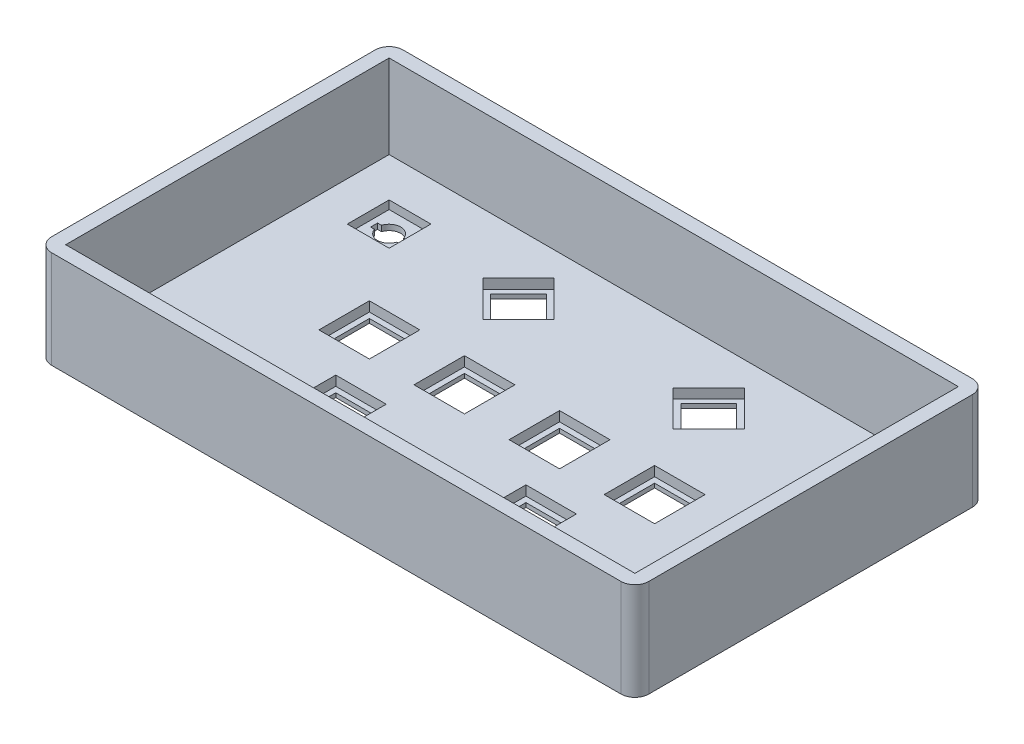
SolidWorks part; units mm, degrees
note: The reader was unsure of these and kept them because the rebuilt part matched: shared geometry of "Sketch1<3>".
ref_plane "Front Plane" through (0, 0, 0) normal (0, 0, 1) x (1, 0, 0)
ref_plane "Top Plane" through (0, 0, 0) normal (0, 1, 0) x (1, 0, 0)
ref_plane "Right Plane" through (0, 0, 0) normal (1, 0, 0) x (0, 0, -1)
sketch "Sketch1" plane through (0, 0, 0) normal (0, 1, 0) x (1, 0, 0)
  line L0 (102.0702, 127.7999) -> (102.0702, -14.5462) construction
  line L1 (0, 0) -> (204.1404, 0)
  line L2 (0, 0) -> (0, 116)
  line L3 (0, 116) -> (204.1404, 116)
  line L4 (204.1404, 0) -> (204.1404, 116)
  line L25 (67.9702, 119.0104) -> (67.9702, -4.6764) construction
  line L26 (43.8702, 65.05) -> (57.9702, 65.05)
  line L31 (43.8702, 65.05) -> (43.8702, 50.95)
  line L32 (43.8702, 50.95) -> (57.9702, 50.95)
  line L33 (25.7608, 94.4142) -> (0, 94.4142) construction
  line L34 (21.5858, 90.2392) -> (21.5858, 116) construction
  line L35 (57.9702, 65.05) -> (57.9702, 50.95)
  line L40 (41.3702, 67.55) -> (41.3702, 48.45) construction
  line L41 (41.3702, 48.45) -> (60.4702, 48.45) construction
  line L42 (60.4702, 67.55) -> (60.4702, 48.45) construction
  line L43 (41.3702, 67.55) -> (60.4702, 67.55) construction
  line L44 (94.5702, 67.55) -> (94.5702, 48.45) construction
  line L45 (94.5702, 48.45) -> (75.4702, 48.45) construction
  line L46 (75.4702, 67.55) -> (75.4702, 48.45) construction
  line L47 (94.5702, 67.55) -> (75.4702, 67.55) construction
  line L48 (92.0702, 50.95) -> (77.9702, 50.95)
  line L49 (77.9702, 65.05) -> (77.9702, 50.95)
  line L50 (92.0702, 65.05) -> (77.9702, 65.05)
  line L51 (92.0702, 65.05) -> (92.0702, 50.95)
  line L52 (13.3874, 28.9) -> (54.844, 28.9) construction
  line L53 (60.9202, 35.95) -> (75.0202, 35.95)
  line L54 (60.9202, 35.95) -> (60.9202, 21.85)
  line L63 (60.9202, 21.85) -> (75.0202, 21.85)
  line L64 (-34.0049, 58) -> (152.0549, 58) construction
  line L65 (75.0202, 35.95) -> (75.0202, 21.85)
  line L66 (48.8702, 38.45) -> (87.0702, 38.45) construction
  line L67 (48.8702, 38.45) -> (48.8702, 19.35) construction
  line L68 (48.8702, 19.35) -> (87.0702, 19.35) construction
  line L69 (87.0702, 38.45) -> (87.0702, 19.35) construction
  line L70 (155.2702, 19.35) -> (117.0702, 19.35) construction
  line L71 (117.0702, 38.45) -> (117.0702, 19.35) construction
  line L72 (155.2702, 38.45) -> (117.0702, 38.45) construction
  line L73 (155.2702, 38.45) -> (155.2702, 19.35) construction
  line L74 (143.2202, 21.85) -> (129.1202, 21.85)
  line L75 (129.1202, 35.95) -> (129.1202, 21.85)
  line L76 (143.2202, 35.95) -> (129.1202, 35.95)
  line L77 (143.2202, 35.95) -> (143.2202, 21.85)
  line L78 (112.0702, 65.05) -> (112.0702, 50.95)
  line L79 (112.0702, 65.05) -> (126.1702, 65.05)
  line L80 (126.1702, 65.05) -> (126.1702, 50.95)
  line L81 (112.0702, 50.95) -> (126.1702, 50.95)
  line L82 (109.5702, 48.45) -> (128.6702, 48.45) construction
  line L83 (109.5702, 67.55) -> (109.5702, 48.45) construction
  line L84 (109.5702, 67.55) -> (128.6702, 67.55) construction
  line L85 (128.6702, 67.55) -> (128.6702, 48.45) construction
  line L86 (162.7702, 48.45) -> (143.6702, 48.45) construction
  line L87 (162.7702, 67.55) -> (162.7702, 48.45) construction
  line L88 (162.7702, 67.55) -> (143.6702, 67.55) construction
  line L89 (143.6702, 67.55) -> (143.6702, 48.45) construction
  line L90 (160.2702, 50.95) -> (146.1702, 50.95)
  line L91 (146.1702, 65.05) -> (146.1702, 50.95)
  line L92 (160.2702, 65.05) -> (146.1702, 65.05)
  line L93 (160.2702, 65.05) -> (160.2702, 50.95)
  line L94 (60.4702, 55.2151) -> (75.4702, 55.2151) construction
  line L95 (94.5702, 55.2151) -> (109.5702, 55.2151) construction
  line L96 (36.5858, 106.0624) -> (36.5858, 87.3701) construction
  line L97 (67.9702, 104.3844) -> (58, 94.4142)
  line L102 (58, 94.4142) -> (67.9702, 84.444)
  line L103 (67.9702, 84.444) -> (77.9404, 94.4142)
  line L104 (77.9404, 94.4142) -> (67.9702, 104.3844)
  line L109 (79.3546, 94.4142) -> (67.9702, 105.7986) construction
  line L110 (67.9702, 105.7986) -> (56.5858, 94.4142) construction
  line L111 (56.5858, 94.4142) -> (67.9702, 83.0298) construction
  line L112 (67.9702, 83.0298) -> (79.3546, 94.4142) construction
  line L113 (136.1702, 83.0298) -> (124.7858, 94.4142) construction
  line L114 (147.5546, 94.4142) -> (136.1702, 83.0298) construction
  line L115 (136.1702, 105.7986) -> (147.5546, 94.4142) construction
  line L116 (124.7858, 94.4142) -> (136.1702, 105.7986) construction
  line L117 (136.1702, 84.444) -> (126.2, 94.4142)
  line L118 (146.1404, 94.4142) -> (136.1702, 84.444)
  line L119 (136.1702, 104.3844) -> (146.1404, 94.4142)
  line L120 (126.2, 94.4142) -> (136.1702, 104.3844)
  line L121 (-5, 0) -> (-5, 116)
  line L122 (0, 121) -> (204.1404, 121)
  line L123 (209.1404, 0) -> (209.1404, 116)
  line L124 (0, -5) -> (204.1404, -5)
  line L125 (209.1404, -5) -> (209.1404, 121) construction
  line L126 (-5, -5) -> (209.1404, -5) construction
  line L127 (-5, 121) -> (209.1404, 121) construction
  line L128 (-5, -5) -> (-5, 121) construction
  line L129 (21.5858, 94.4142) -> (58, 94.4142) construction
  line L131 (21.5858, 58) -> (21.5858, 94.4142) construction
  line L132 (16.1858, 93.1642) -> (26.9858, 93.1642)
  line L133 (16.1858, 93.1642) -> (16.1858, 95.6642)
  line L134 (16.1858, 95.6642) -> (26.9858, 95.6642)
  line L135 (26.9858, 93.1642) -> (26.9858, 95.6642)
  line L136 (16.1858, 93.1642) -> (26.9858, 95.6642) construction
  line L137 (16.1858, 95.6642) -> (26.9858, 93.1642) construction
  line L138 (177.1546, 93.1642) -> (187.9546, 93.1642)
  line L139 (177.1546, 93.1642) -> (177.1546, 95.6642)
  line L140 (177.1546, 95.6642) -> (187.9546, 95.6642)
  line L141 (187.9546, 93.1642) -> (187.9546, 95.6642)
  line L142 (177.1546, 93.1642) -> (187.9546, 95.6642) construction
  line L143 (177.1546, 95.6642) -> (187.9546, 93.1642) construction
  circle A0 centre (21.5858, 94.4142) radius 4.175
  circle A2 centre (21.5858, 94.4142) radius 15 construction
  circle A3 centre (182.5546, 94.4142) radius 15 construction
  circle A4 centre (182.5546, 94.4142) radius 4.175
  arc A6 (0, 121) -> (-5, 116) centre (0, 116) ccw
  arc A7 (-5, 0) -> (0, -5) centre (0, 0) ccw
  arc A8 (204.1404, -5) -> (209.1404, 0) centre (204.1404, 0) ccw
  arc A9 (209.1404, 116) -> (204.1404, 121) centre (204.1404, 116) ccw
  point P31 (67.9702, 35.95)
  point P33 (102.0702, 116)
  point P37 (67.9702, 38.45)
  point P40 (87.0702, 28.9)
  point P41 (75.0202, 28.9)
  point P80 (57.9702, 58)
  point P91 (204.1404, 58)
  dimension "D3" = 8.35
  dimension "D10" = 5
  dimension "D8" = 30
  dimension "D2" = 2.5
  dimension "D4" = 14.1
  dimension "D5" = 2.5
  dimension "D6" = 15
  dimension "D7" = 2.5
  dimension "D9" = 126
  dimension "D11" = 38.2
  dimension "D12" = 10
  dimension "D14" = 20
  dimension "D15" = 10.8
  dimension "D13" = 1
extrude "Boss-Extrude1" add sketch "Sketch1" against normal blind 5 contours L121 L124 L123 L122 L4 L1 L2 L3 | L1 L4 L3 L2 L113 L116 L115 L114 L84 L85 L82 L83 L40 L43 L42 L41 L47 L44 L45 L46 L66 L69 L68 L67 L72 L73 L70 L71 L89 L88 L87 L86 L112 L111 L110 L109 A2 A3 | A2 A0 | L111 L112 L109 L110 L104 L103 L102 L97 | L116 L113 L114 L115 L117 L120 L119 L118 | A3 A4 | L88 L89 L86 L87 L92 L93 L90 L91 | L85 L84 L83 L82 L81 L78 L79 L80 | L44 L47 L46 L45 L50 L51 L48 L49 | L43 L40 L41 L42 L26 L35 L32 L31 | L69 L66 L67 L68 L53 L65 L63 L54 | L73 L72 L71 L70 L76 L77 L74 L75 | L133 L132 L135 L134 | L139 L138 L141 L140
extrude "Boss-Extrude2" add sketch "Sketch1<3>" along normal blind 30 contours L121 L124 L123 L122 L4 L1 L2 L3
sketch "Sketch1<3>" plane through (0, 0, 0) normal (0, 1, 0) x (1, 0, 0) same geometry as "Sketch1"
sketch "Sketch3" plane through (0, 0, 0) normal (0, 1, 0) x (1, 0, 0)
  line L23 (41.8702, 67.05) -> (41.8702, 48.95)
  line L24 (41.8702, 48.95) -> (59.9702, 48.95)
  line L25 (59.9702, 48.95) -> (59.9702, 67.05)
  line L26 (59.9702, 67.05) -> (41.8702, 67.05)
  line L27 (41.8702, 67.05) -> (41.8702, 48.95)
  line L28 (41.8702, 48.95) -> (59.9702, 48.95)
  line L29 (59.9702, 48.95) -> (59.9702, 67.05)
  line L30 (59.9702, 67.05) -> (41.8702, 67.05)
  line L35 (67.9702, 107.2128) -> (55.1716, 94.4142)
  line L36 (80.7688, 94.4142) -> (67.9702, 107.2128)
  line L37 (67.9702, 81.6156) -> (80.7688, 94.4142)
  line L38 (55.1716, 94.4142) -> (67.9702, 81.6156)
  line L39 (67.9702, 107.2128) -> (55.1716, 94.4142)
  line L40 (80.7688, 94.4142) -> (67.9702, 107.2128)
  line L41 (67.9702, 81.6156) -> (80.7688, 94.4142)
  line L42 (55.1716, 94.4142) -> (67.9702, 81.6156)
  line L47 (58.9202, 37.95) -> (58.9202, 19.85)
  line L48 (58.9202, 19.85) -> (77.0202, 19.85)
  line L49 (77.0202, 19.85) -> (77.0202, 37.95)
  line L50 (77.0202, 37.95) -> (58.9202, 37.95)
  line L51 (58.9202, 37.95) -> (58.9202, 19.85)
  line L52 (58.9202, 19.85) -> (77.0202, 19.85)
  line L53 (77.0202, 19.85) -> (77.0202, 37.95)
  line L54 (77.0202, 37.95) -> (58.9202, 37.95)
  line L59 (75.9702, 67.05) -> (75.9702, 48.95)
  line L60 (75.9702, 48.95) -> (94.0702, 48.95)
  line L61 (94.0702, 48.95) -> (94.0702, 67.05)
  line L62 (94.0702, 67.05) -> (75.9702, 67.05)
  line L63 (75.9702, 67.05) -> (75.9702, 48.95)
  line L64 (75.9702, 48.95) -> (94.0702, 48.95)
  line L65 (94.0702, 48.95) -> (94.0702, 67.05)
  line L66 (94.0702, 67.05) -> (75.9702, 67.05)
  line L71 (110.0702, 67.05) -> (110.0702, 48.95)
  line L72 (110.0702, 48.95) -> (128.1702, 48.95)
  line L73 (128.1702, 48.95) -> (128.1702, 67.05)
  line L74 (128.1702, 67.05) -> (110.0702, 67.05)
  line L75 (110.0702, 67.05) -> (110.0702, 48.95)
  line L76 (110.0702, 48.95) -> (128.1702, 48.95)
  line L77 (128.1702, 48.95) -> (128.1702, 67.05)
  line L78 (128.1702, 67.05) -> (110.0702, 67.05)
  line L89 (144.1702, 67.05) -> (144.1702, 48.95)
  line L90 (144.1702, 48.95) -> (162.2702, 48.95)
  line L91 (162.2702, 48.95) -> (162.2702, 67.05)
  line L92 (162.2702, 67.05) -> (144.1702, 67.05)
  line L93 (144.1702, 67.05) -> (144.1702, 48.95)
  line L94 (144.1702, 48.95) -> (162.2702, 48.95)
  line L95 (162.2702, 48.95) -> (162.2702, 67.05)
  line L96 (162.2702, 67.05) -> (144.1702, 67.05)
  line L107 (123.3716, 94.4142) -> (136.1702, 81.6156)
  line L108 (136.1702, 81.6156) -> (148.9688, 94.4142)
  line L109 (148.9688, 94.4142) -> (136.1702, 107.2128)
  line L110 (136.1702, 107.2128) -> (123.3716, 94.4142)
  line L111 (123.3716, 94.4142) -> (136.1702, 81.6156)
  line L112 (136.1702, 81.6156) -> (148.9688, 94.4142)
  line L113 (148.9688, 94.4142) -> (136.1702, 107.2128)
  line L114 (136.1702, 107.2128) -> (123.3716, 94.4142)
  line L119 (127.1202, 37.95) -> (127.1202, 19.85)
  line L120 (127.1202, 19.85) -> (145.2202, 19.85)
  line L121 (145.2202, 19.85) -> (145.2202, 37.95)
  line L122 (145.2202, 37.95) -> (127.1202, 37.95)
  line L123 (127.1202, 37.95) -> (127.1202, 19.85)
  line L124 (127.1202, 19.85) -> (145.2202, 19.85)
  line L125 (145.2202, 19.85) -> (145.2202, 37.95)
  line L126 (145.2202, 37.95) -> (127.1202, 37.95)
  dimension "D1" = 2
  dimension "D2" = 2
  dimension "D3" = 2
  dimension "D4" = 2
  dimension "D5" = 2
  dimension "D6" = 2
  dimension "D7" = 2
  dimension "D8" = 2
extrude "Cut-Extrude1" cut sketch "Sketch3" against normal offset from surface (3.5 mm away) 1.5 up to face at (102.0702, -5, -58)
sketch "Sketch4" plane through (0, 0, 0) normal (0, 1, 0) x (1, 0, 0)
  line L1 (14.0858, 86.9142) -> (29.0858, 86.9142)
  line L2 (14.0858, 86.9142) -> (14.0858, 101.9142)
  line L3 (14.0858, 101.9142) -> (29.0858, 101.9142)
  line L4 (29.0858, 86.9142) -> (29.0858, 101.9142)
  line L5 (14.0858, 86.9142) -> (29.0858, 101.9142) construction
  line L6 (14.0858, 101.9142) -> (29.0858, 86.9142) construction
  line L7 (175.0546, 86.9142) -> (190.0546, 86.9142)
  line L8 (175.0546, 86.9142) -> (175.0546, 101.9142)
  line L9 (175.0546, 101.9142) -> (190.0546, 101.9142)
  line L10 (190.0546, 86.9142) -> (190.0546, 101.9142)
  line L11 (175.0546, 86.9142) -> (190.0546, 101.9142) construction
  line L12 (175.0546, 101.9142) -> (190.0546, 86.9142) construction
  point P0 (21.5858, 94.4142)
  point P6 (182.5546, 94.4142)
  dimension "D1" = 15
extrude "Cut-Extrude2" cut sketch "Sketch4" against normal offset from surface (3 mm away) 2 up to face at (102.0702, -5, -58)
